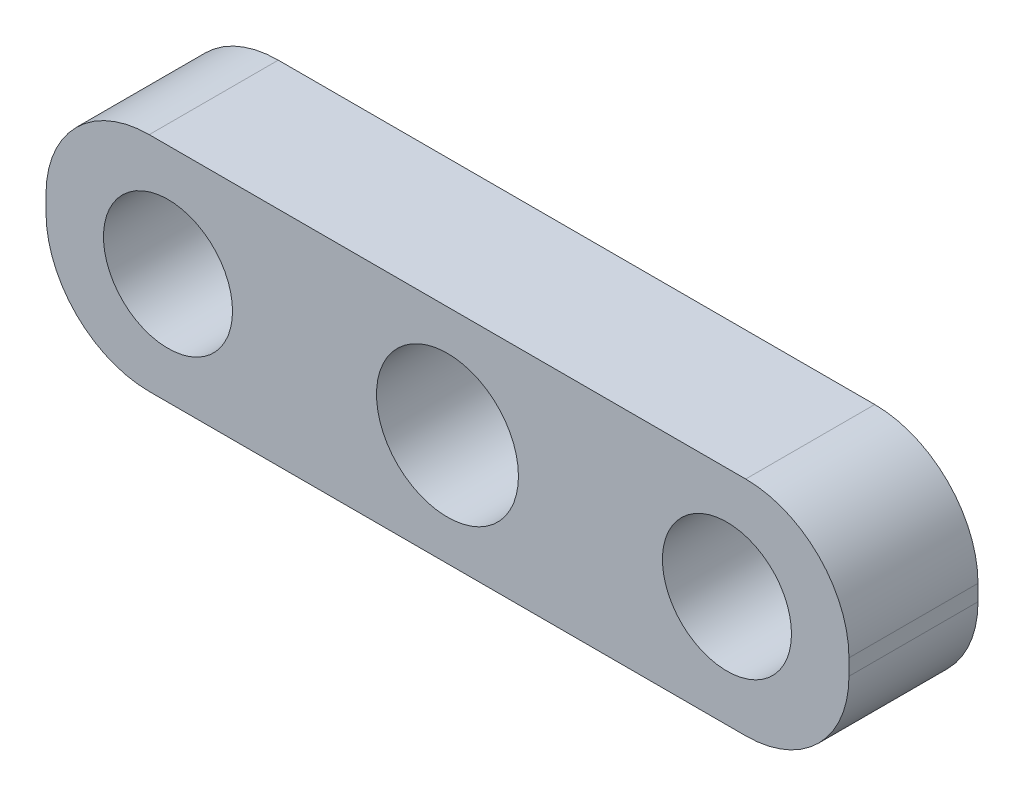
SolidWorks part; units mm, degrees
ref_plane "Front Plane" through (0, 0, 0) normal (0, 0, 1) x (1, 0, 0)
ref_plane "Top Plane" through (0, 0, 0) normal (0, 1, 0) x (1, 0, 0)
ref_plane "Right Plane" through (0, 0, 0) normal (1, 0, 0) x (0, 0, -1)
sketch "Sketch1" plane through (0, 0, 0) normal (0, 0, 1) x (1, 0, 0)
  line L0 (8.4367, -20.4263) -> (8.4367, -17.0625) construction
  line L1 (10.8285, -17.0625) -> (8.4367, -17.0625) construction
  line L2 (17.157, -13.0542) -> (17.157, -7.0708) construction
  line L3 (8.4367, -3.4838) -> (8.4367, 3.4838) construction
  line L4 (17.157, 7.0708) -> (17.157, 13.0542) construction
  line L5 (8.4367, 17.0625) -> (10.8285, 17.0625) construction
  line L6 (8.4367, 17.0625) -> (8.4367, 20.4263) construction
  line L7 (-8.4367, 17.0625) -> (-8.4367, 20.4263) construction
  line L8 (-10.8285, 17.0625) -> (-8.4367, 17.0625) construction
  line L9 (-17.157, 7.0708) -> (-17.157, 13.0542) construction
  line L10 (-8.4367, -3.4838) -> (-8.4367, 3.4838) construction
  line L11 (-17.157, -13.0542) -> (-17.157, -7.0708) construction
  line L12 (-8.4367, -17.0625) -> (-10.8285, -17.0625) construction
  line L13 (-8.4367, -20.4263) -> (-8.4367, -17.0625) construction
  line L14 (-6.9367, -14.3718) -> (-6.9367, -5.7532) construction
  line L15 (-15.5553, -14.3718) -> (-6.9367, -14.3718) construction
  line L16 (-15.5553, -14.3718) -> (-15.5553, -5.7532) construction
  line L17 (-15.5553, -5.7532) -> (-6.9367, -5.7532) construction
  line L18 (6.9367, 14.3718) -> (6.9367, 5.7532) construction
  line L19 (15.5553, 14.3718) -> (6.9367, 14.3718) construction
  line L20 (15.5553, 14.3718) -> (15.5553, 5.7532) construction
  line L21 (15.5553, 5.7532) -> (6.9367, 5.7532) construction
  line L22 (-4.5, 14.5625) -> (-4.5, 5.5625) construction
  line L23 (4.5, 14.5625) -> (-4.5, 14.5625) construction
  line L24 (4.5, 14.5625) -> (4.5, 5.5625) construction
  line L25 (4.5, 5.5625) -> (-4.5, 5.5625) construction
  line L26 (-4.5, -5.5625) -> (-4.5, -14.5625) construction
  line L27 (4.5, -5.5625) -> (-4.5, -5.5625) construction
  line L28 (4.5, -5.5625) -> (4.5, -14.5625) construction
  line L29 (4.5, -14.5625) -> (-4.5, -14.5625) construction
  line L30 (15.5553, -14.3718) -> (6.9367, -14.3718) construction
  line L31 (6.9367, -14.3718) -> (6.9367, -5.7532) construction
  line L32 (15.5553, -5.7532) -> (6.9367, -5.7532) construction
  line L33 (15.5553, -14.3718) -> (15.5553, -5.7532) construction
  line L34 (-15.5553, 14.3718) -> (-6.9367, 14.3718) construction
  line L35 (0, 14.3718) -> (0, 5.7532)
  line L36 (-15.5553, 5.7532) -> (15.5553, 5.7532) construction
  line L37 (-15.5553, 14.3718) -> (-15.5553, 5.7532) construction
  line L39 (-15.5553, 5.7532) -> (15.5553, 5.7532)
  line L40 (-15.5553, 5.7532) -> (-15.5553, 14.3718)
  line L41 (-15.5553, 14.3718) -> (15.5553, 14.3718)
  line L42 (15.5553, 5.7532) -> (15.5553, 14.3718)
  arc A0 (-8.4367, -20.4263) -> (8.4367, -20.4263) centre (0, 0) ccw construction
  arc A1 (10.8285, -17.0625) -> (17.157, -13.0542) centre (10.8285, -10.0625) ccw construction
  arc A2 (17.157, -7.0708) -> (8.4367, -3.4838) centre (10.8285, -10.0625) ccw construction
  arc A3 (8.4367, 3.4838) -> (17.157, 7.0708) centre (10.8285, 10.0625) ccw construction
  arc A4 (17.157, 13.0542) -> (10.8285, 17.0625) centre (10.8285, 10.0625) ccw construction
  arc A5 (8.4367, 20.4263) -> (-8.4367, 20.4263) centre (0, 0) ccw construction
  arc A6 (-10.8285, 17.0625) -> (-17.157, 13.0542) centre (-10.8285, 10.0625) ccw construction
  arc A7 (-17.157, 7.0708) -> (-8.4367, 3.4838) centre (-10.8285, 10.0625) ccw construction
  arc A8 (-8.4367, -3.4838) -> (-17.157, -7.0708) centre (-10.8285, -10.0625) ccw construction
  arc A9 (-17.157, -13.0542) -> (-10.8285, -17.0625) centre (-10.8285, -10.0625) ccw construction
  circle A10 centre (0, 0) radius 4.9125 construction
  circle A11 centre (10.8285, -10.0625) radius 2.5 construction
  circle A12 centre (-10.8285, -10.0625) radius 2.5 construction
  circle A13 centre (-10.8285, 10.0625) radius 2.5 construction
  circle A14 centre (10.8285, 10.0625) radius 2.5 construction
  circle A15 centre (-10.8285, 10.0625) radius 2.5
  circle A16 centre (10.8285, 10.0625) radius 2.5
extrude "Boss-Extrude1" add sketch "Sketch1" along normal blind 5 contours L41 L40 L39 L35 A15 | L39 L42 L41 L35 A16 region at (7.2542, 10.0625, 0) region at (-7.2542, 10.0625, 0)
sketch "Sketch2" plane through (0, 0, 5) normal (0, 0, 1) x (1, 0, 0)
  line L0 (-8.3285, 10.0625) -> (8.3285, 10.0625) construction
  circle A0 centre (-10.8285, 10.0625) radius 2.5 construction
  circle A1 centre (10.8285, 10.0625) radius 2.5 construction
  circle A2 centre (0, 10.0625) radius 2.75
  dimension "D1" = 5.5
extrude "Cut-Extrude1" cut sketch "Sketch2" against normal through all
fillet "Fillet1" radius 4 4 edges at (-15.5553, 14.3718, 2.5) (15.5553, 14.3718, 2.5) (15.5553, 5.7532, 2.5) (-15.5553, 5.7532, 2.5)
